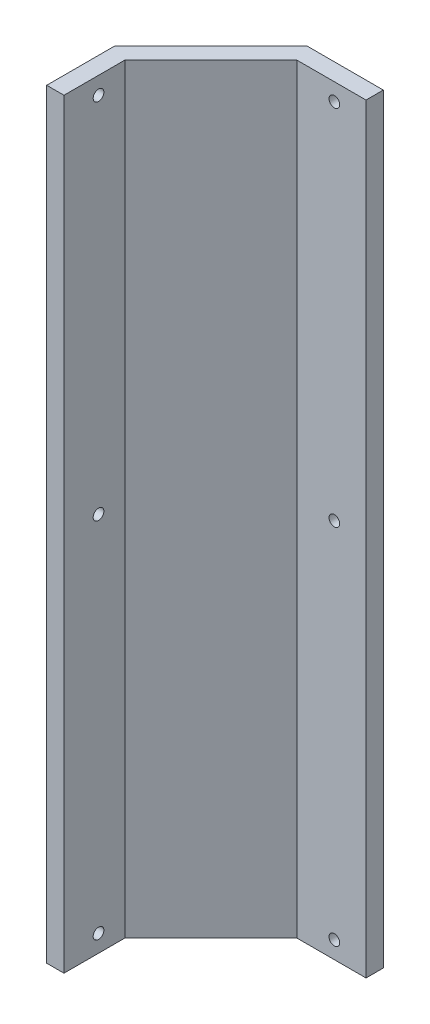
SolidWorks part; units mm, degrees
ref_plane "前视基准面" through (0, 0, 0) normal (0, 0, 1) x (1, 0, 0)
ref_plane "上视基准面" through (0, 0, 0) normal (0, 1, 0) x (1, 0, 0)
ref_plane "右视基准面" through (0, 0, 0) normal (1, 0, 0) x (0, 0, -1)
sketch "草图2" plane through (0, 0, 0) normal (0, 1, 0) x (1, 0, 0)
  line L1 (-87.5233, 42.5) -> (-112.4193, 17.6041)
  line L2 (-112.4193, 17.6041) -> (-112.4193, 0)
  line L8 (-67.5233, 42.5) -> (-87.5233, 42.5)
  line L27 (-117.4193, 19.6751) -> (-117.4193, 0)
  line L28 (-89.5944, 47.5) -> (-117.4193, 19.6751)
  line L29 (-67.5233, 47.5) -> (-89.5944, 47.5)
  line L30 (-27.4193, 17.6041) -> (-39.8672, 30.052) [skipped]
  line L31 (-89.5944, -47.5) -> (-52.3152, -47.5) construction
  line L32 (-87.5233, -42.5) -> (-52.3152, -42.5) construction
  line L33 (-27.4193, -17.6041) -> (-27.4193, 0) [skipped]
  line L34 (-112.4193, 0) -> (-117.4193, 0)
  line L35 (-39.8672, -30.052) -> (-27.4193, -17.6041) [skipped]
  line L36 (-67.5233, 42.5) -> (-67.5233, 47.5)
  line L38 (-52.3152, 47.5) -> (-89.5944, 47.5) construction
  line L39 (-52.3152, 42.5) -> (-87.5233, 42.5) construction
  line L40 (62.5807, 17.6041) -> (37.6848, 42.5) construction
  line L41 (67.5807, 19.6751) -> (39.7559, 47.5) construction
  line L42 (-52.3152, 42.5) -> (2.4767, 42.5) construction
  line L43 (-52.3152, 47.5) -> (2.4767, 47.5) construction
  line L44 (-112.4193, 17.6041) -> (-112.4193, -17.6041) construction
  line L45 (37.6848, 42.5) -> (2.4767, 42.5) construction
  line L46 (39.7559, 47.5) -> (2.4767, 47.5) construction
  line L47 (62.5807, -17.6041) -> (62.5807, 17.6041) construction
  line L48 (67.5807, -19.6751) -> (67.5807, 19.6751) construction
  line L49 (37.6848, -42.5) -> (62.5807, -17.6041) construction
  line L50 (39.7559, -47.5) -> (67.5807, -19.6751) construction
  line L51 (-117.4193, 19.6751) -> (-117.4193, -19.6751) construction
  line L52 (2.4767, -42.5) -> (37.6848, -42.5) construction
  line L53 (2.4767, -47.5) -> (39.7559, -47.5) construction
  line L54 (-52.3152, -47.5) -> (2.4767, -47.5) construction
  line L55 (-52.3152, -42.5) -> (2.4767, -42.5) construction
  line L56 (-117.4193, -19.6751) -> (-89.5944, -47.5) construction
  line L57 (-112.4193, -17.6041) -> (-87.5233, -42.5) [skipped]
  line L58 (-112.4193, -17.6041) -> (-87.5233, -42.5) construction
  line L59 (-87.5233, -42.5) -> (-67.5233, -42.5) [skipped]
  point P0 (-67.5233, 42.5)
  point P12 (0, 0)
  dimension "D1" = 17.6041
  dimension "D4" = 5
  dimension "D5" = 20
  dimension "D2" = 35.2082
extrude "凸台-拉伸1" add sketch "草图2" along normal blind 220
sketch "草图3" plane through (-117.4193, 0, 0) normal (-1, 0, 0) x (0, 0, 1)
  line L1 (-19.6751, 0) -> (0, 0)
  line L2 (-19.6751, 0) -> (-19.6751, 10)
  line L3 (-19.6751, 10) -> (0, 10)
  line L5 (0, 10) -> (0, 0)
  line L6 (-19.6751, 110) -> (0, 110)
  line L7 (0, 220) -> (0, 0) construction
  line L10 (-19.6751, 0) -> (0, 0)
  line L11 (0, 0) -> (0, 220)
  line L12 (0, 220) -> (-19.6751, 220)
  line L13 (-19.6751, 220) -> (-19.6751, 0)
  line L14 (-19.6751, 0) -> (0, 0)
  line L16 (0, 220) -> (-19.6751, 220)
  line L17 (-19.6751, 220) -> (-19.6751, 0)
  line L20 (0, 0) -> (0, 220)
  circle A1 centre (-10, 5) radius 1.55
  circle A2 centre (-10, 215) radius 1.55
  circle A4 centre (-10, 110) radius 1.55
  point P7 (-9.8376, 10)
  point P8 (-9.8376, 10)
  point P28 (0, 110)
  point P29 (-9.8376, 220)
  dimension "D5" = 3.1
  dimension "D6" = 10
  dimension "D4" = 0
extrude "切除-拉伸1" cut sketch "草图3" against normal blind 10 contours A2 | L6 A4 | L6 A4 | A1 region at (-117.4193, 110.6578, -10) region at (-117.4193, 109.3422, -10) region at (-117.4193, 5, -10) region at (-117.4193, 215, -10)
sketch "草图4" plane through (0, 0, -42.5) normal (0, 0, 1) x (1, 0, 0)
  line L0 (-87.5233, 110) -> (-67.5233, 110) construction
  line L1 (-87.5233, 0) -> (-67.5233, 0)
  line L2 (-87.5233, 0) -> (-87.5233, 10)
  line L3 (-87.5233, 10) -> (-67.5233, 10)
  line L4 (-87.5233, 0) -> (-67.5233, 0)
  line L5 (-67.5233, 0) -> (-67.5233, 220)
  line L6 (-67.5233, 220) -> (-87.5233, 220)
  line L7 (-87.5233, 220) -> (-87.5233, 0)
  line L8 (-87.5233, 0) -> (-67.5233, 0)
  line L9 (-67.5233, 0) -> (-67.5233, 220)
  line L10 (-67.5233, 220) -> (-87.5233, 220)
  line L11 (-87.5233, 220) -> (-87.5233, 0)
  line L12 (-67.5233, 0) -> (-67.5233, 10)
  circle A0 centre (-76.6933, 5) radius 1.55
  circle A1 centre (-76.6933, 215) radius 1.55
  circle A2 centre (-76.6933, 110) radius 1.55
  dimension "D3" = 5
  dimension "D5" = 3.1
  dimension "D6" = 3.1
  dimension "D2" = 10
  dimension "D4" = 10.83
  dimension "D1" = 0
extrude "切除-拉伸2" cut sketch "草图4" against normal blind 10 and the other way blind 120 contours A0 | A1 | A2 L0 | L0 A2 region at (-76.6933, 109.3422, -42.5) region at (-76.6933, 110.6578, -42.5) region at (-76.6933, 5, -42.5) region at (-76.6933, 215, -42.5)
